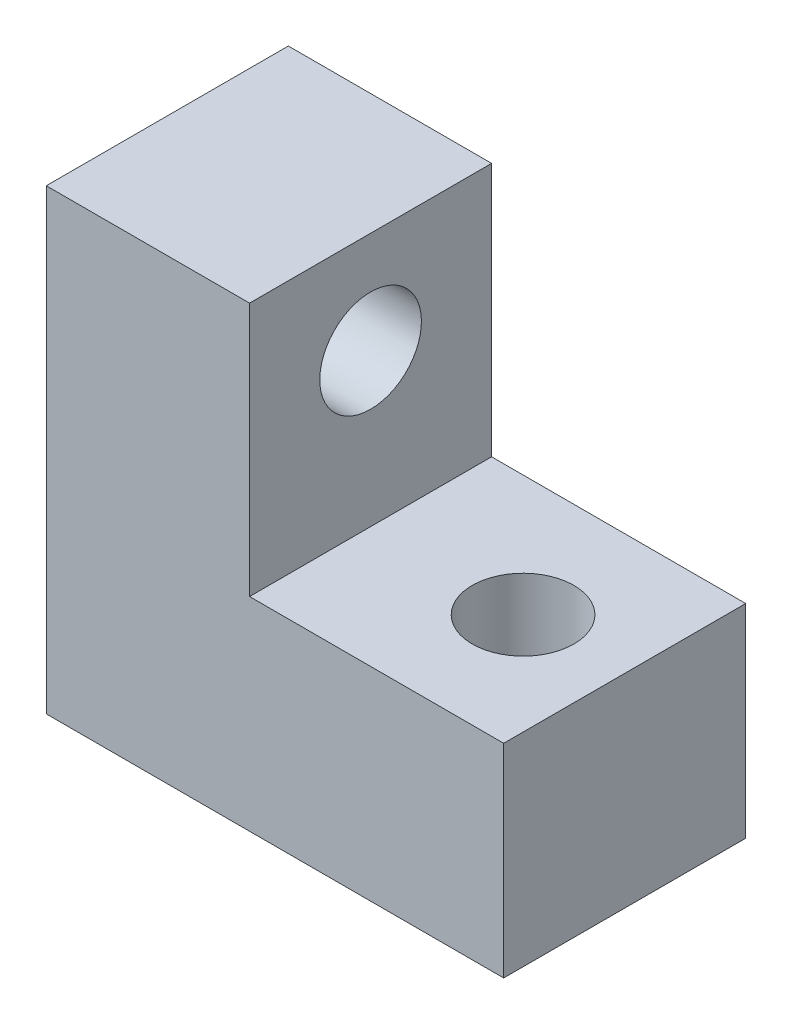
SolidWorks part; units mm, degrees
material "6061 Alloy"
ref_plane "Front Plane" through (0, 0, 0) normal (0, 0, 1) x (1, 0, 0)
ref_plane "Top Plane" through (0, 0, 0) normal (0, 1, 0) x (1, 0, 0)
ref_plane "Right Plane" through (0, 0, 0) normal (1, 0, 0) x (0, 0, -1)
sketch "Sketch1" plane through (0, 0, 0) normal (0, 0, 1) x (1, 0, 0)
  line L0 (9, 9) -> (0, 0) construction
  line L1 (0, 0) -> (18, 0)
  line L2 (0, 0) -> (0, 18)
  line L3 (0, 18) -> (18, 18) construction
  line L4 (18, 0) -> (18, 18) construction
  line L5 (9, 18) -> (9, 0) construction
  line L6 (0, 9) -> (18, 9) construction
  line L7 (0, 18) -> (8, 18)
  line L8 (8, 18) -> (8, 8)
  line L9 (8, 8) -> (18, 8)
  line L10 (18, 8) -> (18, 0)
  point P172 (9, 9)
  dimension "D1" = 8
  dimension "D2" = 18
extrude "3/8" add sketch "Sketch1" along normal blind 9.525
sketch "Sketch2" plane through (0, 0, 0) normal (-1, 0, 0) x (0, 0, 1)
  line L0 (4.7625, 18) -> (4.7625, 14) construction
  line L1 (9.525, 18) -> (0, 18) construction
  circle A0 centre (4.7625, 14) radius 2
  dimension "D1" = 4
  dimension "D2" = 4
extrude "M4_DRILL" cut sketch "Sketch2" against normal up to surface (8 mm away) up to face at (8, 13, 4.7625)
sketch "Sketch3" plane through (0, 0, 0) normal (0, -1, 0) x (-1, 0, 0)
  line L0 (-18, -4.7625) -> (-14, -4.7625) construction
  line L2 (-18, -9.525) -> (-18, 0) construction
  circle A0 centre (-14, -4.7625) radius 2
  dimension "D1" = 4
  dimension "D2" = 4
extrude "M$_DRILL2" cut sketch "Sketch3" against normal up to surface (8 mm away) up to face at (13, 8, 4.7625)
